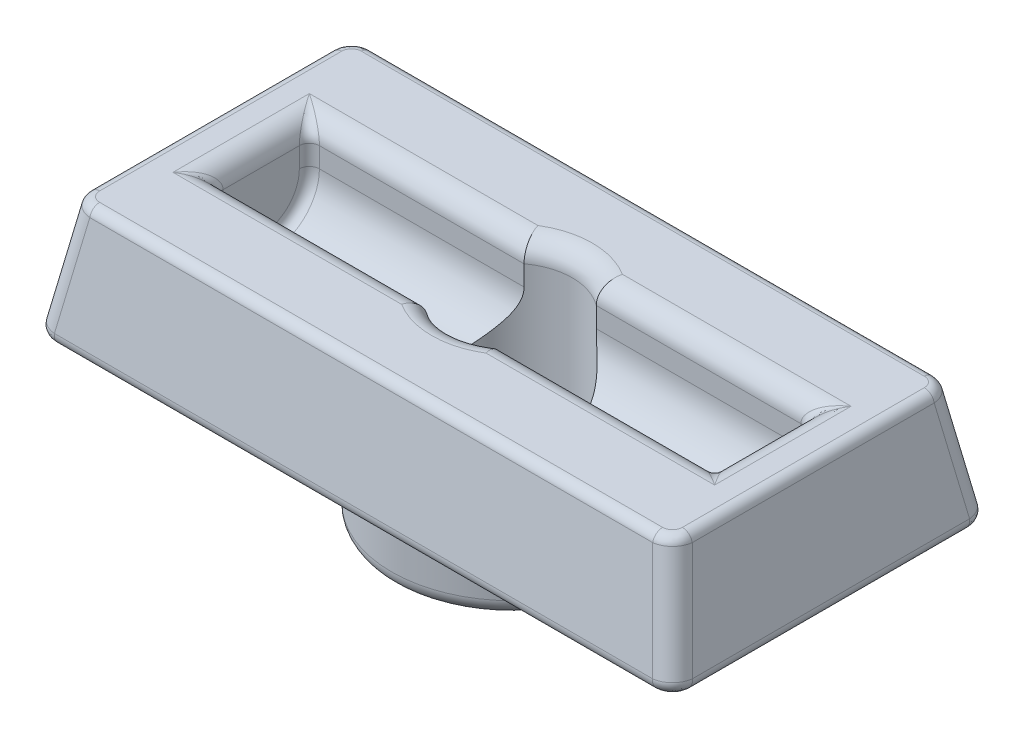
SolidWorks part; units mm, degrees
ref_plane "Front plane" through (0, 0, 0) normal (0, 0, 1) x (1, 0, 0)
ref_plane "Top plane" through (0, 0, 0) normal (0, 1, 0) x (1, 0, 0)
ref_plane "Right plane" through (0, 0, 0) normal (1, 0, 0) x (0, 0, -1)
ref_axis "Axis X" through (0, 0, 0) along (1, 0, 0)
ref_axis "Axis Y" through (0, 0, 0) along (0, 1, 0)
ref_axis "Axis Z" through (0, 0, 0) along (0, 0, 1)
sketch "Sketch1" plane through (0, 0, 0) normal (0, 1, 0) x (1, 0, 0)
  line L1 (-8, 4) -> (8, 4)
  line L2 (-8, 4) -> (-8, -4)
  line L3 (-8, -4) -> (8, -4)
  line L4 (8, 4) -> (8, -4)
  line L5 (-8, 4) -> (8, -4) construction
  line L6 (-8, -4) -> (8, 4) construction
  point P0 (0, 0)
  dimension "D1" = 8
  dimension "D2" = 16
extrude "Extrude1" add sketch "Sketch1" along normal blind 3 draft 10
sketch "Sketch2" plane through (0, 0, 0) normal (1, 0, 0) x (0, 0, -1)
  line L0 (-4, 0) -> (4, 0) construction
  line L1 (-3.471, 3) -> (3.471, 3) construction
  line L2 (-1.2, 2) -> (1.2, 2) construction
  line L3 (-1.2, 2) -> (-1.2, 3)
  line L4 (-1.2, 3) -> (1.2, 3)
  line L5 (1.2, 2) -> (1.2, 3)
  line L6 (0, 2) -> (0, 0) construction
  arc A0 (-1.2, 2) -> (1.2, 2) centre (0, 2) ccw
  arc A1 (0.6633, 3) -> (-1.2, 2) centre (0, 2) ccw construction
  arc A2 (1.2, 2) -> (0.6633, 3) centre (0, 2) ccw construction
  dimension "D2" = 2.4
  dimension "D1" = 2
extrude "Extrude2" cut sketch "Sketch2" against normal blind 6.25 and the other way blind 6.25
sketch "Sketch4" plane through (0, 0, 0) normal (0, -1, 0) x (1, 0, 0)
  circle A0 centre (0, 0) radius 3
  dimension "D1" = 6
extrude "Extrude4" add sketch "Sketch4" along normal blind 2
sketch "Sketch3" plane through (0, 3, 0) normal (0, 1, 0) x (1, 0, 0)
  circle A0 centre (0, 0) radius 1.5
  dimension "D1" = 3
extrude "Extrude3" cut sketch "Sketch3" against normal through all
fillet "Fillet1" radius 0.5 12 edges at (-3.575, 3, -1.2) (-6.25, 3, 0) (-3.575, 3, 1.2) (0, 3, 1.5) (3.575, 3, 1.2) (6.25, 3, 0) (3.575, 3, -1.2) (0, 3, -1.5) (-7.7355, 1.5, -3.7355) (-7.7355, 1.5, 3.7355) (7.7355, 1.5, 3.7355) (7.7355, 1.5, -3.7355)
fillet "Fillet3" radius 0.25 26 edges at (-7.3277, 3, -3.3277) (0, 3, -3.471) (7.3277, 3, -3.3277) (7.471, 3, 0) (7.3277, 3, 3.3277) (0, 3, 3.471) (-7.3277, 3, 3.3277) (6.3964, 2.8536, 1.3464) (6.25, 2.25, 1.2) (6.3964, 2.8536, -1.3464) (6.25, 2.25, -1.2) (-6.3964, 2.8536, 1.3464) (-6.25, 2.25, 1.2) (-6.3964, 2.8536, -1.3464) (-6.25, 2.25, -1.2) (-7.471, 3, 0) (6.25, 0.8, 0) (-6.25, 0.8, 0) (0, 0, 4) (7.8567, 0, 3.8567) (8, 0, 0) (7.8567, 0, -3.8567) (-7.8567, 0, 3.8567) (-8, 0, 0) (-7.8567, 0, -3.8567) (0, 0, -4)
fillet "Fillet4" radius 0.4 1 edges at (0, -2, -3)
equation "\"motor_D\"= 30'Motor diameter"
equation "\"motor_H\"= 13'Motor heigh"
equation "\"motor_d1\"= 25.4558'Seating diameter of screws on the fixed part of the motor"
equation "\"motor_s1\"= 2'Screws diameter on the fixed part of motor"
equation "\"motor_d2\"= 0'Seating diameter of screws on the moving part of the motor (if this parameter is not determine, write 0)"
equation "\"motor_s2\"= 2'Screws diameter on the moving part of motor"
equation "\"motor_Dc\"= 5'Central hole diameter of motor"
equation "\"bearing_d1\"= 6'Bearing inner diameter"
equation "\"bearing_d2\"= 17'Bearing external diameter"
equation "\"bearing h\"= 6'Bearing heigh"
equation "\"pin_d\"= 2'Pin diameter"
equation "\"pin_h\"= 12'Pin heigh"
equation "\"magnet_d1\"= 5'Magnet inner diameter"
equation "\"magnet_d2\"= 9.5'Magnet external diameter"
equation "\"magnet_h\"= 3'Magnet heigh"
equation "\"D1@Sketch1\"=\"pin_d\"+6"
equation "\"D2@Sketch1\"=\"pin_h\"+4"
equation "\"D1@Extrude1\"=\"pin_d\"+1"
equation "\"D1@Sketch2\"=\"pin_d\"/2+1"
equation "\"D2@Sketch2\"=\"pin_d\"+\"print_offset\"*2"
equation "\"D1@Extrude2\"=(\"pin_h\"+0.5)/2"
equation "\"D2@Extrude2\"=(\"pin_h\"+0.5)/2"
equation "\"D1@Sketch3\"= \"bearing_d1\" / 2"
equation "\"D1@Sketch4\"=\"bearing_d1\""
equation "\"D1@Extrude4\"=\"bearing h\"/3"
equation "\"motor_a2\"= 10'Seating parameter in rectangle of screws on the moving part of the motor"
equation "\"motor_b2\"= 22'Seating parameter in rectangle of screws on the moving part of the motor"
equation "\"motor_cmd\"= 12'Central magnet mount diameter"
equation "\"motor_cmh\"= 1.4'Central magnet mount heigh (if not write 0)"
equation "\"motor_whR\"= 10'Distance from center of motor to wires"
equation "\"print_offset\"= 0.2'Offset for printing holes"
equation "\"ft_sensor_d1\"= 9.8"
equation "\"ft_sensor_d2\"= 24.9"
equation "\"ft_sensor_d3\"= 22.6'Inner diameter of "
equation "\"ft_sensor_h\"= 7.1"
equation "\"ft_sensor_whD\"= 5"
